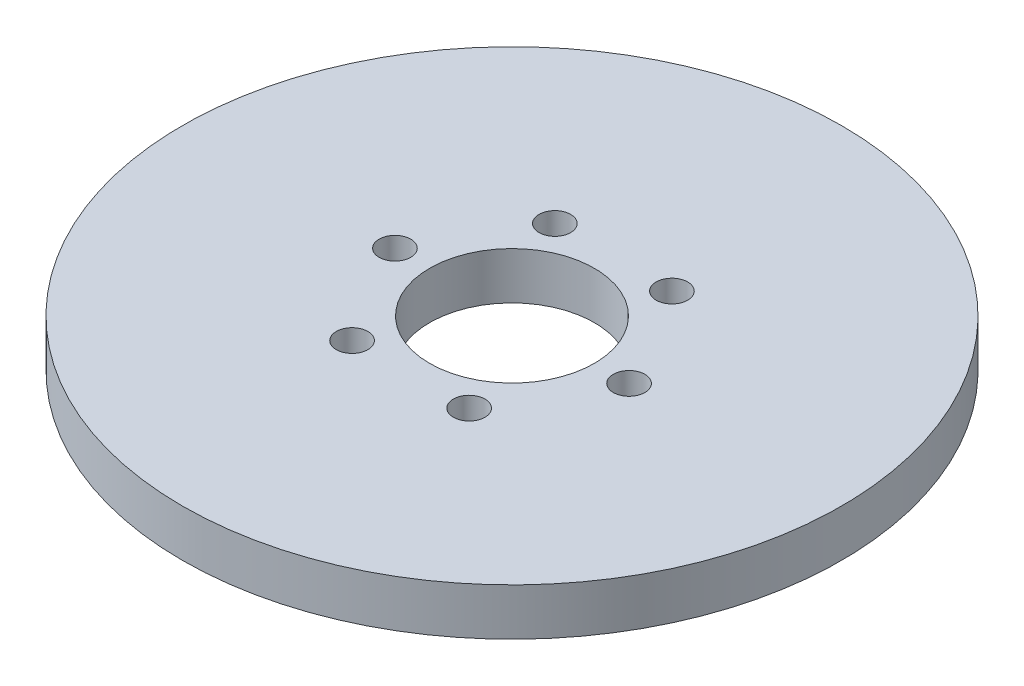
SolidWorks part; units mm, degrees
ref_plane "Front Plane" through (0, 0, 0) normal (0, 0, 1) x (1, 0, 0)
ref_plane "Top Plane" through (0, 0, 0) normal (0, 1, 0) x (1, 0, 0)
ref_plane "Right Plane" through (0, 0, 0) normal (1, 0, 0) x (0, 0, -1)
sketch "Sketch1" plane through (0, 0, 0) normal (0, 1, 0) x (1, 0, 0)
  circle A0 centre (0, 0) radius 70
  dimension "FLANGE_OD" = 140
extrude "Boss-Extrude1" add sketch "Sketch1" along normal blind 10
sketch "Sketch2" plane through (0, 0, 0) normal (0, 1, 0) x (1, 0, 0)
  circle A0 centre (0, 0) radius 17.5
  dimension "BORE_D" = 35
extrude "Cut-Extrude1" cut sketch "Sketch2" along normal through all
sketch "Sketch3" plane through (0, 10, 0) normal (0, 1, 0) x (1, 0, 0)
  circle A0 centre (0, 0) radius 24.8663 construction
  circle A1 centre (-24.8663, 0) radius 3.3567
  dimension "BOLT_D" = 6.7135
  dimension "BOLT_PCD" = 49.7326
extrude "Cut-Extrude2" cut sketch "Sketch3" against normal blind 9.1772
pattern_circular "CirPattern1" count 6 over 360 about axis through (0, 0, 0) along (0, 1, 0) of "Cut-Extrude2"
